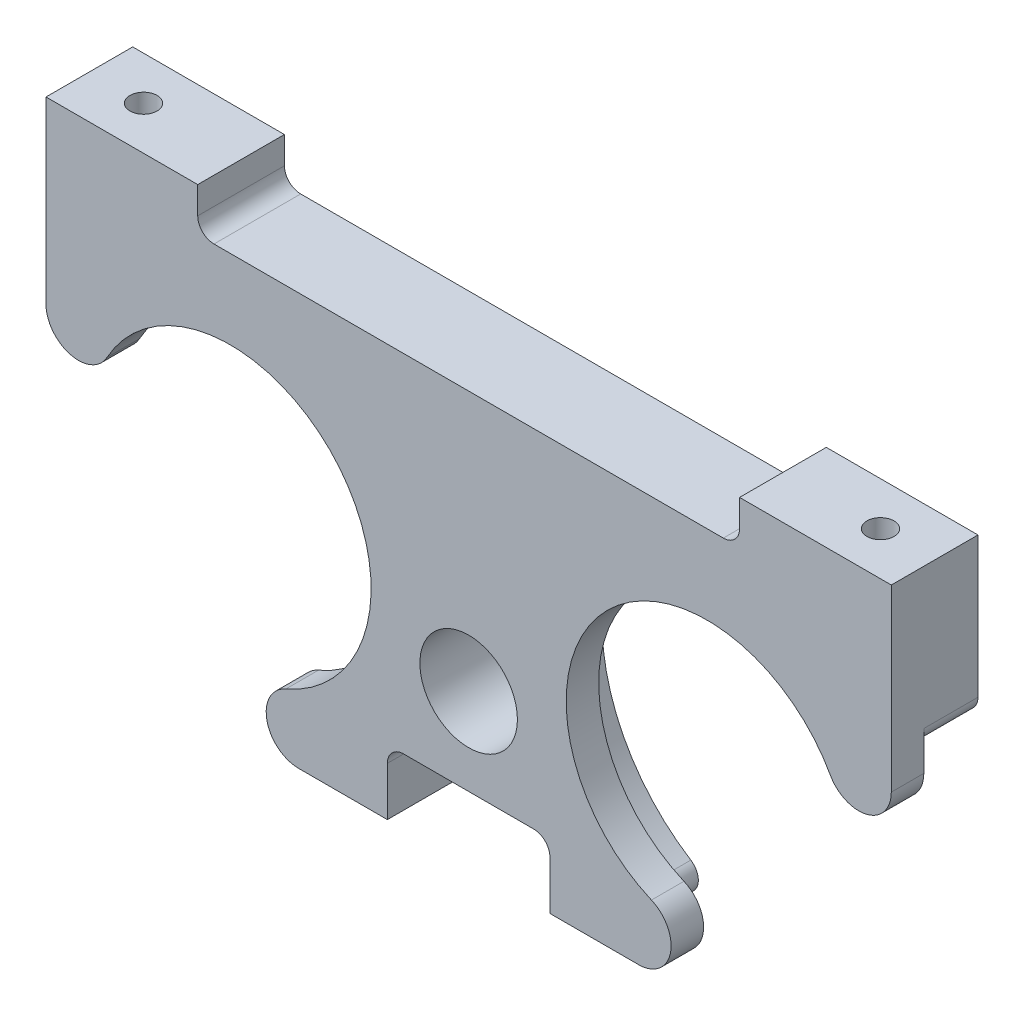
SolidWorks part; units mm, degrees
material "POM Acetal Copolymer"
ref_plane "Front Plane" through (0, 0, 0) normal (0, 0, 1) x (1, 0, 0)
ref_plane "Top Plane" through (0, 0, 0) normal (0, 1, 0) x (1, 0, 0)
ref_plane "Right Plane" through (0, 0, 0) normal (1, 0, 0) x (0, 0, -1)
sketch "Sketch1" plane through (0, 0, 0) normal (0, 0, 1) x (1, 0, 0)
  line L1 (-39, 0) -> (39, 0)
  line L2 (-39, 0) -> (-39, 42)
  line L3 (-39, 42) -> (39, 42)
  line L4 (39, 0) -> (39, 42)
  dimension "D1" = 42
  dimension "D2" = 78
extrude "Boss-Extrude1" add sketch "Sketch1" along normal blind 8
sketch "Sketch2" plane through (0, 0, 0) normal (0, 0, -1) x (-1, 0, 0)
  line L1 (39, 42) -> (39, 0) construction
  line L2 (-39, 0) -> (-39, 42) construction
  line L3 (-39, 29.0309) -> (-39, 0)
  line L5 (-11.6947, 0) -> (-39, 0)
  line L6 (39, 0) -> (39, 29.0309)
  line L9 (11.6947, 0) -> (39, 0)
  line L10 (39, 0) -> (-39, 0) construction
  arc A0 (-36.2891, 28.1457) -> (-12.4998, 2.7656) centre (-22, 17.7) cw
  arc A1 (36.2891, 28.1457) -> (12.4998, 2.7656) centre (22, 17.7) ccw
  arc A2 (-12.4998, 2.7656) -> (-11.6947, 0) centre (-11.6947, 1.5) ccw
  arc A4 (36.2891, 28.1457) -> (39, 29.0309) centre (37.5, 29.0309) ccw
  arc A5 (-36.2891, 28.1457) -> (-39, 29.0309) centre (-37.5, 29.0309) cw
  arc A6 (11.6947, 0) -> (12.4998, 2.7656) centre (11.6947, 1.5) ccw
  dimension "D2" = 17.7
  dimension "D5" = 1.5
  dimension "D1" = 44
  dimension "D3" = 17.7
  dimension "D4" = 22
extrude "Cut-Extrude2" cut sketch "Sketch2" against normal blind 5
sketch "Sketch3" plane through (0, 0, 8) normal (0, 0, 1) x (1, 0, 0)
  circle A0 centre (0, 14) radius 4.5
  dimension "D2" = 9
  dimension "D1" = 14
extrude "Cut-Extrude3" cut sketch "Sketch3" against normal up to next
sketch "Sketch4" plane through (0, 0, 0) normal (0, 0, -1) x (-1, 0, 0)
  line L0 (-39, 0) -> (-11.6947, 0) construction
  line L1 (-39, 29.0309) -> (-39, 0) construction
  line L2 (39, 0) -> (39, 29.0309) construction
  line L3 (11.6947, 0) -> (39, 0) construction
  line L4 (-39, 25.446) -> (-39, 0)
  line L5 (-39, 0) -> (-15.6826, 0)
  line L6 (15.6826, 0) -> (39, 0)
  line L7 (39, 0) -> (39, 25.446)
  line L8 (-39, 42) -> (39, 42) construction
  line L9 (-25, 42) -> (25, 42)
  line L10 (-25, 42) -> (-25, 38)
  line L11 (-25, 38) -> (25, 38)
  line L12 (25, 42) -> (25, 38)
  line L13 (11.6947, 0) -> (-11.6947, 0) construction
  line L14 (-7.5, 0) -> (7.5, 0)
  line L15 (-7.5, 0) -> (-7.5, 4.5)
  line L16 (-6, 6) -> (6, 6)
  line L17 (7.5, 0) -> (7.5, 4.5)
  arc A0 (-33.375, 23.9936) -> (-16.8671, 5.7562) centre (-22, 17.7) cw
  arc A1 (33.375, 23.9936) -> (16.8671, 5.7562) centre (22, 17.7) ccw
  arc A2 (-16.8671, 5.7562) -> (-15.6826, 0) centre (-15.6826, 3) ccw
  arc A3 (-33.375, 23.9936) -> (-39, 25.446) centre (-36, 25.446) cw
  arc A4 (33.375, 23.9936) -> (39, 25.446) centre (36, 25.446) ccw
  arc A5 (16.8671, 5.7562) -> (15.6826, 0) centre (15.6826, 3) cw
  arc A6 (6, 6) -> (7.5, 4.5) centre (6, 4.5) cw
  arc A7 (-7.5, 4.5) -> (-6, 6) centre (-6, 4.5) cw
  dimension "D1" = 13
  dimension "D2" = 3
  dimension "D8" = 1.5
  dimension "D3" = 50
  dimension "D4" = 25
  dimension "D5" = 4
  dimension "D6" = 15
  dimension "D7" = 6
extrude "Cut-Extrude4" cut sketch "Sketch4" against normal up to next
fillet "Fillet1" radius 1.5 2 edges at (-25, 38, 4) (25, 38, 4)
hole_wizard "Tap Drill for M3 Tap1" positions "Sketch6" profile "Sketch5" hole size "M3" standard "ISO"
sketch "Sketch6" plane through (0, 42, 0) normal (0, 1, 0) x (-1, 0, 0)
  line L0 (-39, 0) -> (-25, 0) construction
  line L1 (-39, 8) -> (-39, 0) construction
  line L2 (39, 8) -> (39, 0) construction
  point P0 (-34, 4)
  point P3 (34, 4)
  dimension "D1" = 4
  dimension "D2" = 5
  dimension "D3" = 5
sketch "Sketch5" plane through (34, 42, 4) normal (1, 0, 0) x (0, 0, 1)
  line L0 (0, 0) -> (0, 10.7511)
  line L1 (0, 10.7511) -> (1.25, 10)
  line L2 (1.25, 10) -> (1.25, 0)
  line L5 (1.25, 0) -> (0, 0)
  line L10 (0, 10.7511) -> (-1.25, 10) construction
  line L11 (0, -6.35) -> (0, 107.95) construction
  dimension "Hole Dia." = 2.5
  dimension "Hole Depth" = 10
  dimension "Drill Angle" = 118
